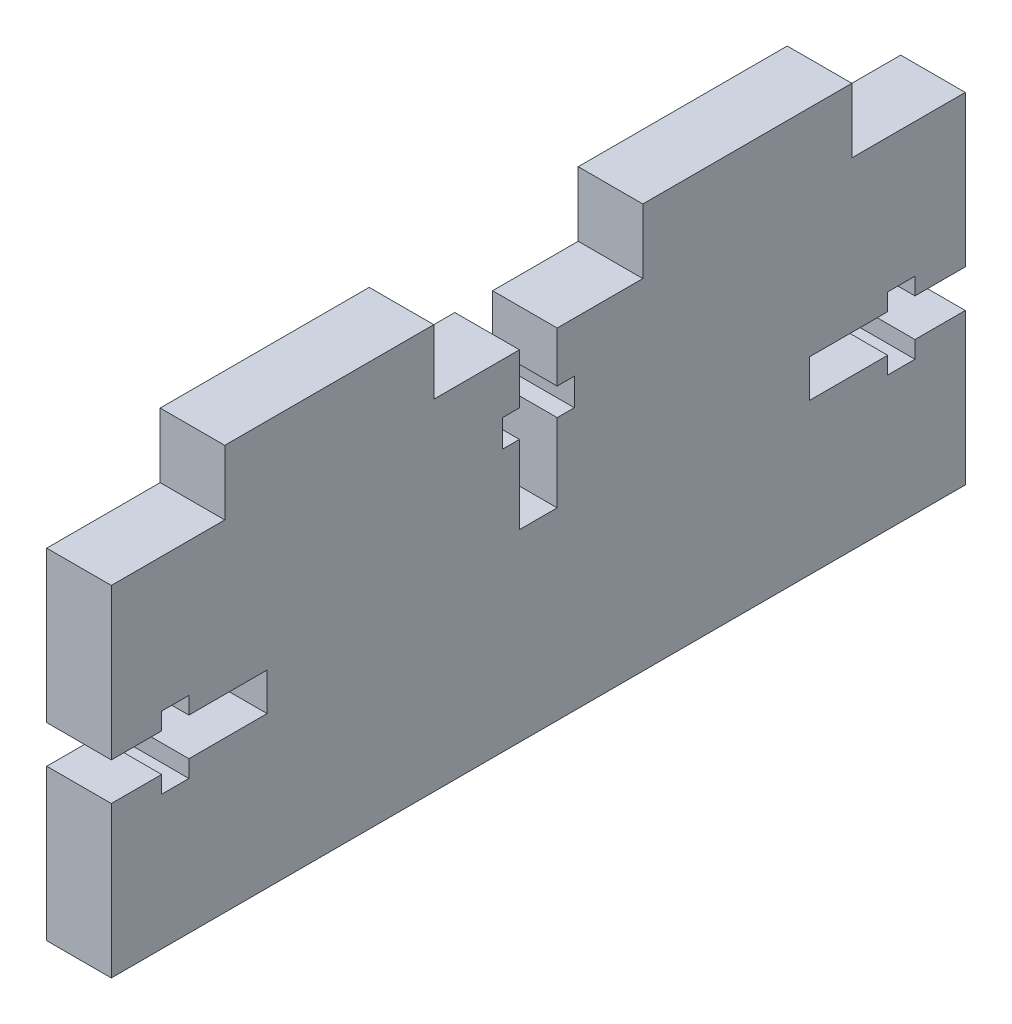
SolidWorks part; units mm, degrees
ref_plane "Front Plane" through (0, 0, 0) normal (0, 0, 1) x (1, 0, 0)
ref_plane "Top Plane" through (0, 0, 0) normal (0, 1, 0) x (1, 0, 0)
ref_plane "Right Plane" through (0, 0, 0) normal (1, 0, 0) x (0, 0, -1)
sketch "Sketch2" plane through (0, 0, 0) normal (1, 0, 0) x (0, 0, -1)
  line L1 (-52.4957, 23.777) -> (15.3223, 23.777)
  line L2 (-52.4957, 23.777) -> (-52.4957, -3.223)
  line L3 (-52.4957, -3.223) -> (15.3223, -3.223)
  line L4 (15.3223, 23.777) -> (15.3223, -3.223)
  dimension "D1" = 67.818
  dimension "D2" = 27
extrude "Boss-Extrude1" add sketch "Sketch2" along normal blind 5.13
sketch "Sketch3" plane through (0, 23.777, 0) normal (0, 1, 0) x (1, 0, 0)
  line L0 (0, 15.3223) -> (0, -52.4957) construction
  line L1 (0, 6.3133) -> (5.13, 6.3133)
  line L2 (0, 6.3133) -> (0, -10.2867)
  line L3 (0, -10.2867) -> (5.13, -10.2867)
  line L4 (5.13, 6.3133) -> (5.13, -10.2867)
  line L5 (5.13, 15.3223) -> (5.13, -52.4957) construction
  line L6 (5.13, 15.3223) -> (0, 15.3223) construction
  line L10 (0, -26.8867) -> (0, -43.4867)
  line L11 (0, -26.8867) -> (5.13, -26.8867)
  line L12 (5.13, -26.8867) -> (5.13, -43.4867)
  line L13 (0, -43.4867) -> (5.13, -43.4867)
  dimension "D2" = 49.8
  dimension "D3" = 16.6
  dimension "D4" = 9.009
  dimension "D1" = 2
extrude "Boss-Extrude2" add sketch "Sketch3" along normal blind 5.13
sketch "Sketch6" plane through (5.13, 0, 0) normal (1, 0, 0) x (0, 0, -1)
  line L0 (-20.0852, 23.777) -> (-20.0852, 19.782)
  line L1 (-17.0882, 19.782) -> (-17.0882, 23.777)
  line L2 (-15.7292, 19.782) -> (-17.0882, 19.782)
  line L3 (-17.0882, 17.615) -> (-15.7292, 17.615)
  line L4 (-15.7292, 17.615) -> (-15.7292, 19.782)
  line L5 (-20.0852, 19.782) -> (-21.4442, 19.782)
  line L6 (-21.4442, 17.615) -> (-20.0852, 17.615)
  line L7 (-21.4442, 19.782) -> (-21.4442, 17.615)
  line L8 (-20.0852, 11.408) -> (-17.0882, 11.408)
  line L9 (-17.0882, 11.408) -> (-17.0882, 17.615)
  line L10 (-20.0852, 17.615) -> (-20.0852, 11.408)
  line L12 (15.3223, -3.223) -> (15.3223, 23.777) construction
  point P12 (-18.5867, 11.408)
  dimension "D1" = 33.909
extrude "Cut-Extrude3" cut sketch "Sketch6" against normal through all and the other way through all
ref_axis "Axis1" through (5.13, -3.223, 18.5867) along (0, 1, 0)
sketch "Sketch4" plane through (5.13, 0, 0) normal (1, 0, 0) x (0, 0, -1)
  line L0 (-52.4957, -3.223) -> (15.3223, -3.223) construction
  line L1 (-52.4957, 8.7785) -> (-48.5007, 8.7785)
  line L2 (-48.5007, 11.7755) -> (-52.4957, 11.7755)
  line L3 (-48.5007, 13.1345) -> (-48.5007, 11.7755)
  line L4 (-46.3337, 11.7755) -> (-46.3337, 13.1345)
  line L5 (-46.3337, 13.1345) -> (-48.5007, 13.1345)
  line L6 (-48.5007, 8.7785) -> (-48.5007, 7.4195)
  line L7 (-46.3337, 7.4195) -> (-46.3337, 8.7785)
  line L8 (-48.5007, 7.4195) -> (-46.3337, 7.4195)
  line L9 (-40.1267, 8.7785) -> (-40.1267, 11.7755)
  line L10 (-40.1267, 11.7755) -> (-46.3337, 11.7755)
  line L11 (-46.3337, 8.7785) -> (-40.1267, 8.7785)
  point P0 (-40.1267, 10.277)
  dimension "D1" = 13.5
extrude "t-slot" cut sketch "Sketch4" against normal through all and the other way through all
sketch "Sketch7" plane through (5.13, 0, 0) normal (1, 0, 0) x (0, 0, -1)
  line L0 (-52.4957, -3.223) -> (15.3223, -3.223) construction
  line L1 (15.3223, 11.7755) -> (11.3273, 11.7755)
  line L2 (11.3273, 8.7785) -> (15.3223, 8.7785)
  line L3 (11.3273, 7.4195) -> (11.3273, 8.7785)
  line L4 (9.1603, 8.7785) -> (9.1603, 7.4195)
  line L5 (9.1603, 7.4195) -> (11.3273, 7.4195)
  line L6 (11.3273, 11.7755) -> (11.3273, 13.1345)
  line L7 (9.1603, 13.1345) -> (9.1603, 11.7755)
  line L8 (11.3273, 13.1345) -> (9.1603, 13.1345)
  line L9 (2.9533, 11.7755) -> (2.9533, 8.7785)
  line L10 (2.9533, 8.7785) -> (9.1603, 8.7785)
  line L11 (9.1603, 11.7755) -> (2.9533, 11.7755)
  point P0 (2.9533, 10.277)
  dimension "D1" = 13.5
extrude "Cut-Extrude6" cut sketch "Sketch7" against normal through all and the other way through all
equation "\"D4@Sketch3\" = (\"D1@Sketch2\"-\"D2@Sketch3\")/2"
equation "\"D1@Sketch4\" = \"D2@Sketch2\"/2"
equation "\"D1@Sketch7\" = \"D2@Sketch2\"/2"
equation "\"D1@Sketch6\" = \"D1@Sketch2\"/2"
